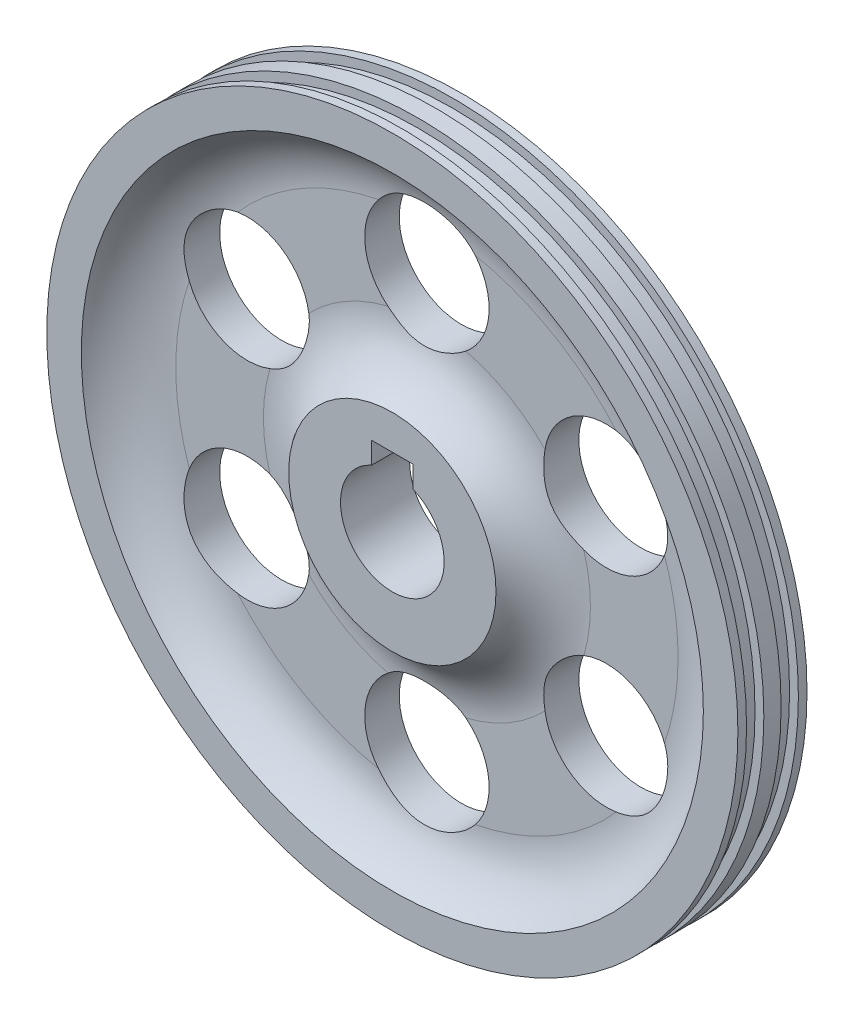
SolidWorks part; units mm, degrees
ref_plane "Ön Düzlem" through (0, 0, 0) normal (0, 0, 1) x (1, 0, 0)
ref_plane "Üst Düzlem" through (0, 0, 0) normal (0, 1, 0) x (1, 0, 0)
ref_plane "Sağ Düzlem" through (0, 0, 0) normal (1, 0, 0) x (0, 0, -1)
sketch "Çizim1" plane through (0, 0, 0) normal (1, 0, 0) x (0, 0, -1)
  line L0 (0, 0) -> (10, 0) construction
  line L1 (-0.2766, 7.5) -> (9.7234, 7.5)
  line L2 (9.7234, 7.5) -> (9.7234, 50)
  line L3 (9.7234, 50) -> (8.4734, 50)
  line L4 (-0.2766, 50) -> (-0.2766, 45)
  line L5 (0.9734, 50) -> (0.9734, 48.7278)
  line L6 (0.9734, 48.7278) -> (3.4734, 48.7278)
  line L7 (3.4734, 48.7278) -> (3.4734, 50)
  line L8 (5.9734, 50) -> (5.9734, 48.7278)
  line L9 (5.9734, 48.7278) -> (8.4734, 48.7278)
  line L10 (8.4734, 48.7278) -> (8.4734, 50)
  line L11 (0.9734, 50) -> (-0.2766, 50)
  line L12 (5.9734, 50) -> (3.4734, 50)
  line L13 (-0.2766, 45) -> (4.7234, 45)
  line L14 (4.7234, 45) -> (4.7234, 15)
  line L15 (4.7234, 15) -> (-0.2766, 15)
  line L16 (-0.2766, 15) -> (-0.2766, 7.5)
  point P17 (-0.2766, 47.5)
  dimension "D1" = 10
  dimension "D2" = 1.25
  dimension "D3" = 2.5
  dimension "D4" = 2.5
  dimension "D5" = 7.5
  dimension "D6" = 50
  dimension "D7" = 45
  dimension "D8" = 15
  dimension "D9" = 5
revolve "Döndür1" add sketch "Çizim1" angle 360 about L0
fillet "Radyus11" radius 10 1 edges at (15, 0, -4.7234)
fillet "Radyus12" radius 10 1 edges at (45, 0, -4.7234)
sketch "Çizim2" plane through (0, 0, 0.2766) normal (0, 0, 1) x (1, 0, 0)
  line L1 (-3, 10) -> (3, 10)
  line L2 (-3, 10) -> (-3, 6.8739)
  line L4 (3, 10) -> (3, 6.8739)
  circle A0 centre (0, 0) radius 7.5 construction
  arc A2 (3, 6.8739) -> (-3, 6.8739) centre (0, 0) ccw
  circle A3 centre (0, 30) radius 9
  circle A4 centre (25.9808, 15) radius 9
  circle A5 centre (25.9808, -15) radius 9
  circle A6 centre (0, -30) radius 9
  circle A7 centre (-25.9808, -15) radius 9
  circle A8 centre (-25.9808, 15) radius 9
  point P21 (0, 0)
  dimension "D3" = 18
  dimension "D1" = 10
  dimension "D2" = 6
  dimension "D4" = 30
  dimension "D5" = 6
extrude "Kes-Ekstrüzyon1" cut sketch "Çizim2" against normal blind 45 contours L2 A2 L4 L1 | A3 | A8 | A4 | A5 | A6 | A7
